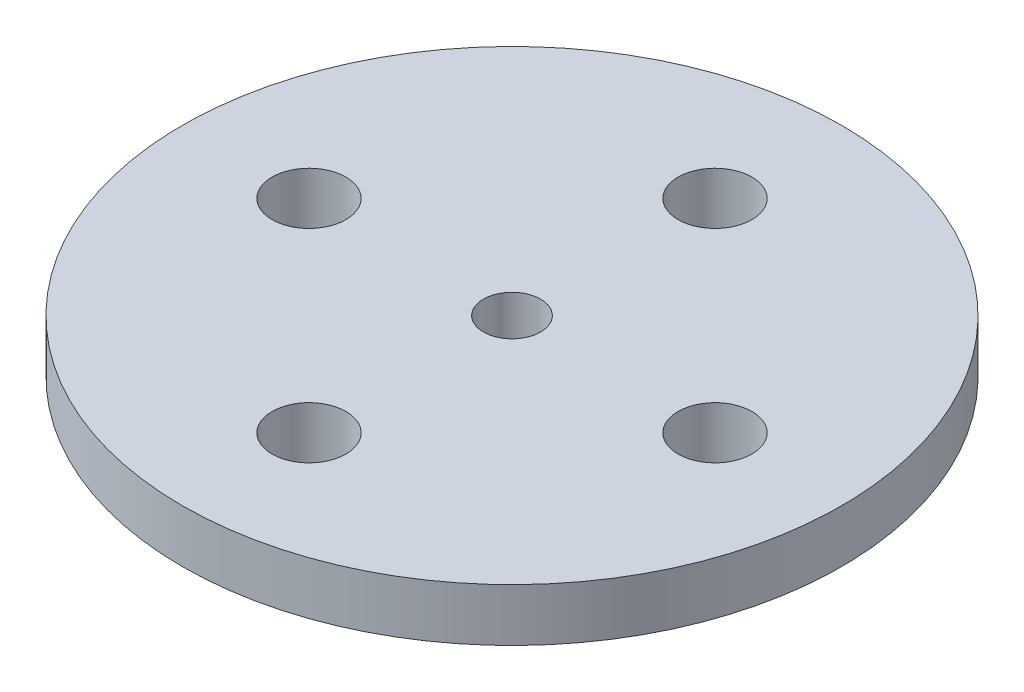
SolidWorks part; units mm, degrees
ref_plane "Front Plane" through (0, 0, 0) normal (0, 0, 1) x (1, 0, 0)
ref_plane "Top Plane" through (0, 0, 0) normal (0, 1, 0) x (1, 0, 0)
ref_plane "Right Plane" through (0, 0, 0) normal (1, 0, 0) x (0, 0, -1)
sketch "Sketch1" plane through (0, 0, 0) normal (0, 1, 0) x (1, 0, 0)
  line L0 (0, 15.5) -> (0, -15.5) construction
  line L1 (-15.5, 0) -> (15.5, 0) construction
  line L2 (-2.4674, 13.4022) -> (-4, 4) construction
  line L3 (4, -4) -> (-4, -4) construction
  line L4 (4, -4) -> (4, 4) construction
  line L5 (4, 4) -> (-4, 4) construction
  line L6 (-4, -4) -> (-4, 4) construction
  line L7 (4, -4) -> (-4, 4) construction
  line L8 (4, 4) -> (-4, -4) construction
  line L9 (-4, 4) -> (-2.4674, 13.4022)
  line L10 (4, 4) -> (2.4674, 13.4022)
  line L11 (4, -4) -> (2.4674, -13.4022)
  line L12 (-4, -4) -> (-2.4674, -13.4022)
  line L13 (-4, 4) -> (-12.5927, 2.4331) construction
  line L14 (-4, 4) -> (-12.4485, 2.4594)
  line L15 (-4, -4) -> (-12.4485, -2.4594)
  line L16 (4, -4) -> (12.4485, -2.4594)
  line L17 (4, 4) -> (12.4485, 2.4594)
  circle A0 centre (0, 0) radius 15.5 construction
  circle A1 centre (0, 0) radius 14.5 construction
  arc A2 (2.4674, 13.4022) -> (-2.4674, 13.4022) centre (0, 13) ccw
  arc A3 (2.4674, -13.4022) -> (-2.4674, -13.4022) centre (0, -13) cw
  arc A4 (-12.4485, 2.4594) -> (-12.4485, -2.4594) centre (-12, 0) ccw
  arc A5 (12.4485, 2.4594) -> (12.4485, -2.4594) centre (12, 0) cw
  circle A6 centre (0, 0) radius 12 construction
  circle A7 centre (0, 0) radius 9.5 construction
  circle A8 centre (0, 0) radius 7.5 construction
  circle A9 centre (0, 12) radius 0.5
  circle A10 centre (0, 9.5) radius 0.5
  circle A11 centre (0, 7.5) radius 0.5
  circle A12 centre (12, 0) radius 0.5
  circle A13 centre (9.5, 0) radius 0.5
  circle A14 centre (7.5, 0) radius 0.5
  circle A15 centre (0, -12) radius 0.5
  circle A16 centre (0, -9.5) radius 0.5
  circle A17 centre (0, -7.5) radius 0.5
  circle A18 centre (-12, 0) radius 0.5
  circle A19 centre (-9.5, 0) radius 0.5
  circle A20 centre (-7.5, 0) radius 0.5
  circle A21 centre (0, 0) radius 1.375
  point P59 (0, 0)
  dimension "D1" = 31
  dimension "D2" = 1
  dimension "D3" = 5
  dimension "D4" = 5
  dimension "D5" = 8
  dimension "D6" = 8
  dimension "D7" = 15
  dimension "D9" = 24
  dimension "D11" = 1
  dimension "D12" = 1
  dimension "D13" = 4
  dimension "D8" = 19
  dimension "D10" = 1
  dimension "D14" = 2.75
extrude "Boss-Extrude1" add sketch "Sketch1" along normal blind 2
sketch "Sketch4" plane through (0, 0, 0) normal (0, -1, 0) x (1, 0, 0)
  circle A0 centre (0, 0) radius 4.5635
  circle A1 centre (0, 0) radius 2.5635
  dimension "D1" = 9.127
  dimension "D2" = 2
extrude "Boss-Extrude3" add sketch "Sketch4" along normal blind 2.5
sketch "Sketch5" plane through (0, -2.5, 0) normal (0, -1, 0) x (1, 0, 0)
  line L0 (0, 0) -> (0, 0.6245) construction
  line L1 (0, 3.0508) -> (-0.2909, 2.5469)
  line L2 (0, 3.0508) -> (0.2909, 2.5469)
  line L3 (0.9427, 2.9015) -> (0.5104, 2.5122)
  line L4 (0.9427, 2.9015) -> (1.0637, 2.3324)
  line L5 (1.7932, 2.4681) -> (1.2617, 2.2315)
  line L6 (1.7932, 2.4681) -> (1.7324, 1.8895)
  line L7 (2.4681, 1.7932) -> (1.8895, 1.7324)
  line L8 (2.4681, 1.7932) -> (2.2315, 1.2617)
  line L9 (2.9015, 0.9427) -> (2.3324, 1.0637)
  line L10 (2.9015, 0.9427) -> (2.5122, 0.5104)
  line L11 (3.0508, 0) -> (2.5469, 0.2909)
  line L12 (3.0508, 0) -> (2.5469, -0.2909)
  line L13 (2.9015, -0.9427) -> (2.5122, -0.5104)
  line L14 (2.9015, -0.9427) -> (2.3324, -1.0637)
  line L15 (2.4681, -1.7932) -> (2.2315, -1.2617)
  line L16 (2.4681, -1.7932) -> (1.8895, -1.7324)
  line L17 (1.7932, -2.4681) -> (1.7324, -1.8895)
  line L18 (1.7932, -2.4681) -> (1.2617, -2.2315)
  line L19 (0.9427, -2.9015) -> (1.0637, -2.3324)
  line L20 (0.9427, -2.9015) -> (0.5104, -2.5122)
  line L21 (0, -3.0508) -> (0.2909, -2.5469)
  line L22 (0, -3.0508) -> (-0.2909, -2.5469)
  line L23 (-0.9427, -2.9015) -> (-0.5104, -2.5122)
  line L24 (-0.9427, -2.9015) -> (-1.0637, -2.3324)
  line L25 (-1.7932, -2.4681) -> (-1.2617, -2.2315)
  line L26 (-1.7932, -2.4681) -> (-1.7324, -1.8895)
  line L27 (-2.4681, -1.7932) -> (-1.8895, -1.7324)
  line L28 (-2.4681, -1.7932) -> (-2.2315, -1.2617)
  line L29 (-2.9015, -0.9427) -> (-2.3324, -1.0637)
  line L30 (-2.9015, -0.9427) -> (-2.5122, -0.5104)
  line L31 (-3.0508, 0) -> (-2.5469, -0.2909)
  line L32 (-3.0508, 0) -> (-2.5469, 0.2909)
  line L33 (-2.9015, 0.9427) -> (-2.5122, 0.5104)
  line L34 (-2.9015, 0.9427) -> (-2.3324, 1.0637)
  line L35 (-2.4681, 1.7932) -> (-2.2315, 1.2617)
  line L36 (-2.4681, 1.7932) -> (-1.8895, 1.7324)
  line L37 (-1.7932, 2.4681) -> (-1.7324, 1.8895)
  line L38 (-1.7932, 2.4681) -> (-1.2617, 2.2315)
  line L39 (-0.9427, 2.9015) -> (-1.0637, 2.3324)
  line L40 (-0.9427, 2.9015) -> (-0.5104, 2.5122)
  circle A0 centre (0, 0) radius 2.5635 construction
  arc A1 (-2.2315, 1.2617) -> (-2.3324, 1.0637) centre (0, 0) ccw
  arc A2 (-1.7324, 1.8895) -> (-1.8895, 1.7324) centre (0, 0) ccw
  arc A3 (-1.0637, 2.3324) -> (-1.2617, 2.2315) centre (0, 0) ccw
  arc A4 (-0.2909, 2.5469) -> (-0.5104, 2.5122) centre (0, 0) ccw
  arc A5 (0.5104, 2.5122) -> (0.2909, 2.5469) centre (0, 0) ccw
  arc A6 (1.2617, 2.2315) -> (1.0637, 2.3324) centre (0, 0) ccw
  arc A7 (1.8895, 1.7324) -> (1.7324, 1.8895) centre (0, 0) ccw
  arc A8 (2.3324, 1.0637) -> (2.2315, 1.2617) centre (0, 0) ccw
  arc A9 (2.5469, 0.2909) -> (2.5122, 0.5104) centre (0, 0) ccw
  arc A10 (2.5122, -0.5104) -> (2.5469, -0.2909) centre (0, 0) ccw
  arc A11 (2.2315, -1.2617) -> (2.3324, -1.0637) centre (0, 0) ccw
  arc A12 (1.7324, -1.8895) -> (1.8895, -1.7324) centre (0, 0) ccw
  arc A13 (1.0637, -2.3324) -> (1.2617, -2.2315) centre (0, 0) ccw
  arc A14 (0.2909, -2.5469) -> (0.5104, -2.5122) centre (0, 0) ccw
  arc A15 (-0.5104, -2.5122) -> (0, -2.5635) centre (0, 0) ccw
  arc A16 (-1.2617, -2.2315) -> (-1.0637, -2.3324) centre (0, 0) ccw
  arc A17 (-1.8895, -1.7324) -> (-1.7324, -1.8895) centre (0, 0) ccw
  arc A18 (-2.3324, -1.0637) -> (-2.2315, -1.2617) centre (0, 0) ccw
  arc A19 (-2.5469, -0.2909) -> (-2.5122, -0.5104) centre (0, 0) ccw
  arc A20 (-2.5122, 0.5104) -> (-2.5469, 0.2909) centre (0, 0) ccw
  point P68 (0, 0)
  circle M5 centre (0, 0) radius 2.5635
  dimension "D1" = 30
  dimension "D2" = 3.0508
  dimension "D3" = 20
extrude "Cut-Extrude3" cut sketch "Sketch5" against normal up to surface (2.5 mm away) contours L36 L35 M5 | L34 L33 M5 | L32 L31 M5 | L30 L29 M5 | L28 L27 M5 | L26 L25 M5 | L24 L23 M5 | L0 L21 M5 | L22 L0 M5 | L20 L19 M5 | L18 L17 M5 | L16 L15 M5 | L14 L13 M5 | L12 L11 M5 | L10 L9 M5 | L8 L7 M5 | L6 L5 M5 | L4 L3 M5 | L0 L2 M5 | L0 L1 M5 | L40 L39 M5 | L38 L37 M5 region at (0, -2.5, 2.7223) region at (-0.8412, -2.5, 2.5891) region at (0.8412, -2.5, 2.5891) region at (-1.6001, -2.5, 2.2024) region at (1.6001, -2.5, 2.2024) region at (-2.2024, -2.5, 1.6001) region at (2.2024, -2.5, 1.6001) region at (-2.5891, -2.5, 0.8412) region at (2.5891, -2.5, 0.8412) region at (-2.7223, -2.5, 0) region at (2.7223, -2.5, 0) region at (-2.5891, -2.5, -0.8412) region at (2.5891, -2.5, -0.8412) region at (-2.2024, -2.5, -1.6001) region at (2.2024, -2.5, -1.6001) region at (-1.6001, -2.5, -2.2024) region at (1.6001, -2.5, -2.2024) region at (-0.8412, -2.5, -2.5891) region at (0.8412, -2.5, -2.5891) region at (0, -2.5, -2.7223) up to face at (0, 0, 1.375)
sketch "Sketch6" plane through (0, 2, 0) normal (0, 1, 0) x (1, 0, 0)
  circle A0 centre (0, 0) radius 15.875
  circle A2 centre (0, 0) radius 3.75
  dimension "D1" = 31.75
extrude "Boss-Extrude6" add sketch "Sketch6" against normal blind 2.54
sketch "Sketch7" plane through (0, 2, 0) normal (0, 1, 0) x (1, 0, 0)
  circle A0 centre (0, 9.779) radius 1.778
extrude "Cut-Extrude4" cut sketch "Sketch7" against normal blind 2.54
pattern_circular "CirPattern1" count 4 over 360 about axis through (0, 2, 0) along (0, -1, 0) of "Cut-Extrude4"
